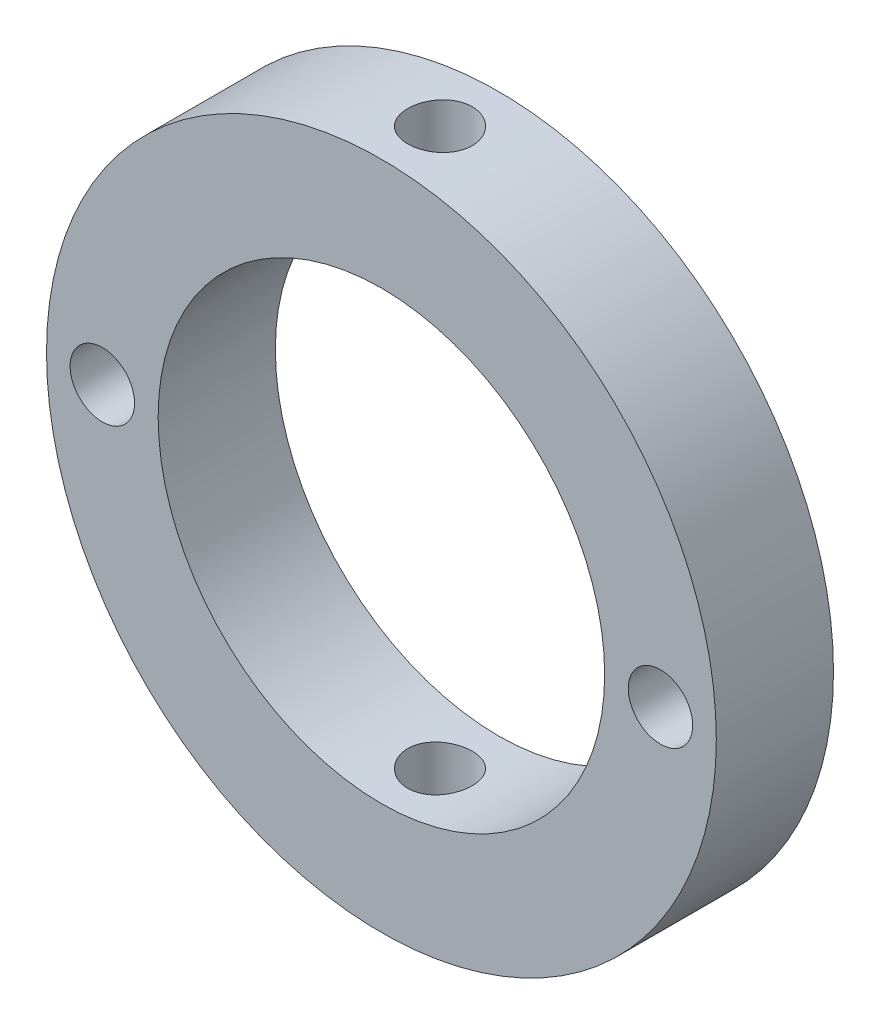
SolidWorks part; units mm, degrees
ref_plane "Front Plane" through (0, 0, 0) normal (0, 0, 1) x (1, 0, 0)
ref_plane "Top Plane" through (0, 0, 0) normal (0, 1, 0) x (1, 0, 0)
ref_plane "Right Plane" through (0, 0, 0) normal (1, 0, 0) x (0, 0, -1)
sketch "Sketch1" plane through (0, 0, 0) normal (0, 0, 1) x (1, 0, 0)
  circle A0 centre (0, 0) radius 28.575
  dimension "D1" = 57.15
extrude "Boss-Extrude1" add sketch "Sketch1" along normal blind 10
sketch "Sketch2" plane through (0, 0, 10) normal (0, 0, 1) x (1, 0, 0)
  circle A0 centre (0, 0) radius 19.05
  dimension "D1" = 38.1
extrude "Cut-Extrude1" cut sketch "Sketch2" against normal through all
ref_plane "Plane1" through (0, 28.575, 0) normal (0, 1, 0) x (1, 0, 0)
sketch "Sketch5" plane through (0, 28.575, 0) normal (0, 1, 0) x (1, 0, 0)
  circle A0 centre (0, -5) radius 2.75
  dimension "D2" = 5.5
  dimension "D1" = 5
extrude "Cut-Extrude2" cut sketch "Sketch5" against normal through all
sketch "Sketch6" plane through (0, 0, 10) normal (0, 0, 1) x (1, 0, 0)
  line L0 (0, 28.575) -> (0, -28.575) construction
  line L1 (5.5, 28.575) -> (-5.5, 28.575) construction
  circle A0 centre (-23.8125, 0) radius 2.75
  circle A1 centre (0, 0) radius 28.575 construction
  circle A2 centre (23.8125, 0) radius 2.75
  dimension "D2" = 5.5
  dimension "D1" = 23.8125
extrude "Cut-Extrude3" cut sketch "Sketch6" against normal through all
